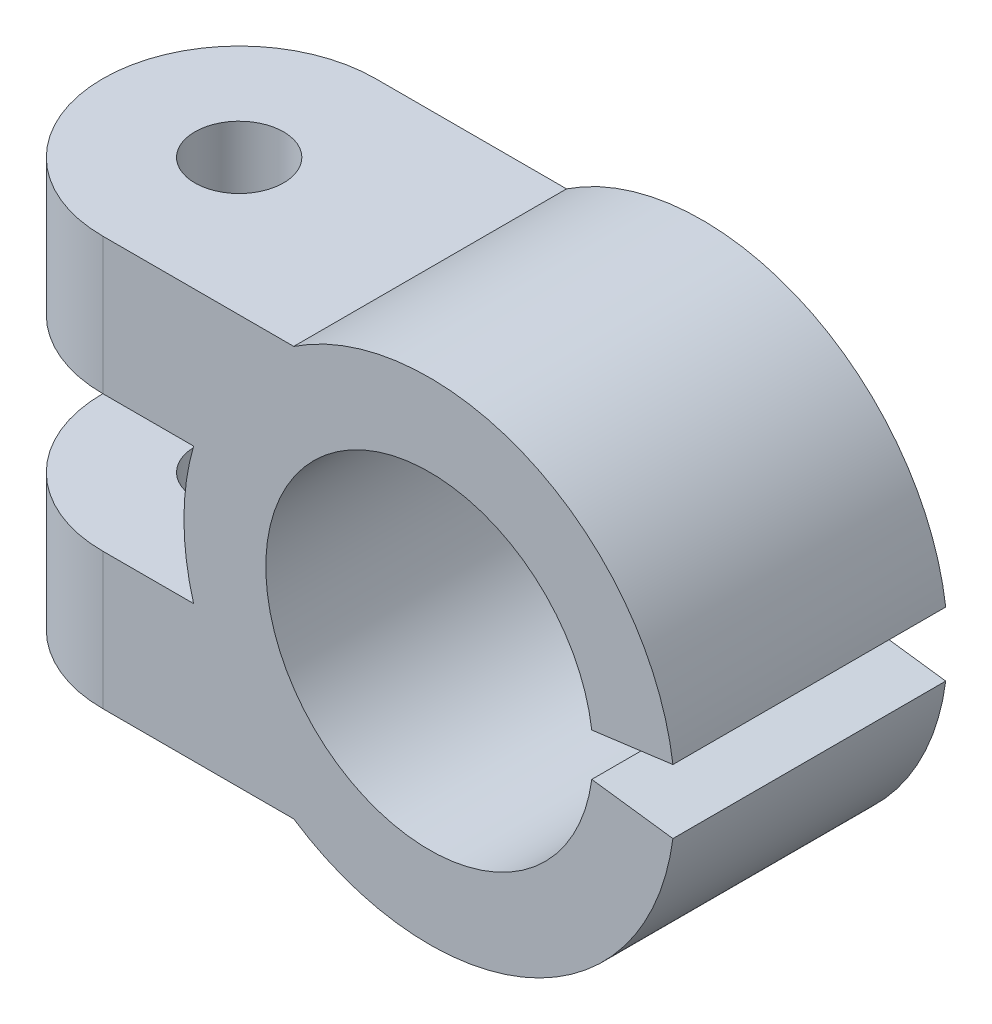
SolidWorks part; units mm, degrees
ref_plane "Alzado" through (0, 0, 0) normal (0, 0, 1) x (1, 0, 0)
ref_plane "Planta" through (0, 0, 0) normal (0, 1, 0) x (1, 0, 0)
ref_plane "Vista lateral" through (0, 0, 0) normal (1, 0, 0) x (0, 0, -1)
sketch "Croquis1" plane through (0, 0, 0) normal (0, 0, 1) x (1, 0, 0)
  circle A0 centre (0, 0) radius 6
  circle A1 centre (0, 0) radius 9
  dimension "D1" = 12
  dimension "D2" = 3
extrude "Saliente-Extruir1" add sketch "Croquis1" along normal blind 10
sketch "Croquis2" plane through (0, 0, 10) normal (0, 0, 1) x (1, 0, 0)
  line L0 (0, 0) -> (8.923, 1.1747)
  line L2 (8.923, -1.1747) -> (0, 0)
  line L4 (0, 0) -> (9, 0) construction
  circle A0 centre (0, 0) radius 9 construction
  arc A1 (8.923, -1.1747) -> (8.923, 1.1747) centre (0, 0) ccw
  dimension "D1" = 15
  dimension "D2" = 7.5
extrude "Cortar-Extruir1" cut sketch "Croquis2" against normal through all
sketch "Croquis3" plane through (0, 0, 10) normal (0, 0, 1) x (1, 0, 0)
  line L0 (-4.9749, 7.5) -> (-16.9749, -7.5) construction
  line L1 (-4.9749, 7.5) -> (-16.9749, 7.5)
  line L3 (-4.9749, -7.5) -> (-16.9749, -7.5)
  line L4 (-16.9749, 7.5) -> (-16.9749, -7.5)
  line L5 (0, 0) -> (-10.9749, 0) construction
  arc A0 (8.923, 1.1747) -> (8.923, -1.1747) centre (0, 0) ccw construction
  arc A1 (-4.9749, 7.5) -> (-4.9749, -7.5) centre (0, 0) ccw
  dimension "D1" = 12
  dimension "D2" = 15
extrude "Saliente-Extruir2" add sketch "Croquis3" against normal up to surface (10 mm away) up to face at (-0.0321, 0, 0)
fillet "Redondeo1" radius 5 2 edges at (-16.9749, 0, 0) (-16.9749, 0, 10)
sketch "Croquis4" plane through (0, -7.5, 0) normal (0, -1, 0) x (1, 0, 0)
  circle A0 centre (-11.9749, 5) radius 1.625
  arc A2 (-11.9749, 10) -> (-16.9749, 5) centre (-11.9749, 5) ccw construction
  dimension "D1" = 3.25
extrude "Cortar-Extruir2" cut sketch "Croquis4" against normal through all
sketch "Croquis5" plane through (0, 0, 10) normal (0, 0, 1) x (1, 0, 0)
  line L0 (-21.8086, -2.5) -> (-8.6458, 2.5) construction
  line L1 (-8.6458, 2.5) -> (-21.8086, 2.5)
  line L3 (-8.6458, -2.5) -> (-21.8086, -2.5)
  line L4 (-21.8086, 2.5) -> (-21.8086, -2.5)
  line L5 (-15.2272, 0) -> (0, 0) construction
  arc A1 (-8.6458, 2.5) -> (-8.6458, -2.5) centre (0, 0) ccw
  arc A2 (8.923, 1.1747) -> (-4.9749, 7.5) centre (0, 0) ccw construction
  dimension "D1" = 5
extrude "Cortar-Extruir4" cut sketch "Croquis5" against normal through all
sketch "Croquis6" plane through (0, 0, 0) normal (0, 1, 0) x (1, 0, 0)
  circle A0 centre (-11.9749, -5) radius 5.5
  dimension "D1" = 11
extrude "Cortar-Extruir5" cut sketch "Croquis6" against normal mid plane 5
sketch "Croquis7" plane through (0, -7.5, 0) normal (0, -1, 0) x (1, 0, 0)
  line L1 (-8.7995, 5) -> (-10.3872, 7.75)
  line L2 (-10.3872, 7.75) -> (-13.5627, 7.75)
  line L3 (-13.5627, 7.75) -> (-15.1504, 5)
  line L4 (-15.1504, 5) -> (-13.5627, 2.25)
  line L5 (-13.5627, 2.25) -> (-10.3872, 2.25)
  line L6 (-10.3872, 2.25) -> (-8.7995, 5)
  circle A0 centre (-11.9749, 5) radius 2.75 construction
  dimension "D1" = 5.5
extrude "Cortar-Extruir6" cut sketch "Croquis7" against normal blind 2.3
